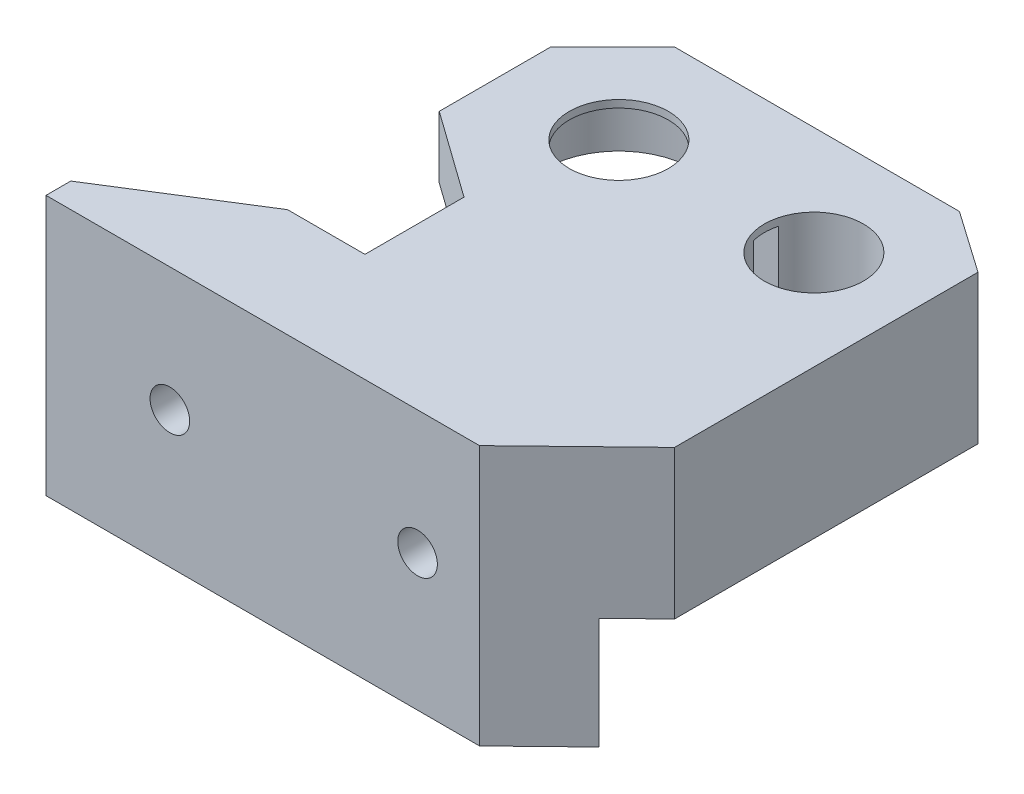
SolidWorks part; units mm, degrees
ref_plane "Front Plane" through (0, 0, 0) normal (0, 0, 1) x (1, 0, 0)
ref_plane "Top Plane" through (0, 0, 0) normal (0, 1, 0) x (1, 0, 0)
ref_plane "Right Plane" through (0, 0, 0) normal (1, 0, 0) x (0, 0, -1)
sketch "Sketch1" plane through (0, 0, 0) normal (0, 1, 0) x (1, 0, 0)
  line L0 (0, 0) -> (15.75, 0) construction
  line L5 (-4.25, 8.75) -> (18.75, 8.75)
  line L6 (18.75, 8.75) -> (23.75, 5.25)
  line L7 (23.75, 5.25) -> (23.75, -19.25)
  line L8 (23.75, -19.25) -> (15.75, -27)
  line L9 (15.75, -27) -> (-19.25, -27)
  line L10 (-19.25, -27) -> (-19.25, -25)
  line L11 (-19.25, -25) -> (-8.5, -18.25)
  line L12 (-8.5, -18.25) -> (-2.25, -18.25)
  line L13 (-2.25, -18.25) -> (-2.25, -10.25)
  line L14 (-2.25, -10.25) -> (-9.25, -5.25)
  line L15 (-9.25, -5.25) -> (-9.25, 3.75)
  line L16 (-9.25, 3.75) -> (-4.25, 8.75)
  line L17 (15.75, 0) -> (23.75, 0) construction
  circle A0 centre (0, 0) radius 4
  circle A1 centre (15.75, 0) radius 4
  point P0 (0, 0)
  dimension "D2" = 8
  dimension "D3" = 8
  dimension "D1" = 15.75
  dimension "D4" = 23
  dimension "D5" = 5
  dimension "D6" = 3.5
  dimension "D7" = 24.5
  dimension "D8" = 8
  dimension "D9" = 8.75
  dimension "D10" = 5
  dimension "D11" = 5
  dimension "D12" = 7
  dimension "D13" = 5
  dimension "D14" = 9
  dimension "D15" = 8
  dimension "D16" = 7.75
  dimension "D17" = 35
  dimension "D18" = 6.25
  dimension "D19" = 6.75
  dimension "D20" = 2
extrude "Boss-Extrude1" add sketch "Sketch1" along normal blind 5
sketch "Sketch2" plane through (0, 0, 0) normal (0, -1, 0) x (1, 0, 0)
  line L0 (23.75, 19.25) -> (23.75, -5.25)
  line L1 (23.75, -5.25) -> (20.25, -5.25)
  line L2 (20.25, -5.25) -> (20.25, 18.25)
  line L3 (20.25, 18.25) -> (-8.5, 18.25)
  line L4 (-8.5, 18.25) -> (-14.8704, 22.25)
  line L5 (-8.5, 18.25) -> (-19.25, 25) construction
  line L6 (-14.8704, 22.25) -> (20.6532, 22.25)
  line L7 (15.75, 27) -> (23.75, 19.25) construction
  line L8 (20.6532, 22.25) -> (23.75, 19.25)
  dimension "D1" = 3.5
  dimension "D2" = 4
extrude "Boss-Extrude2" add sketch "Sketch2" along normal blind 7
sketch "Sketch3" plane through (0, 0, 0) normal (0, -1, 0) x (1, 0, 0)
  line L5 (-14.8704, 22.25) -> (20.6532, 22.25)
  line L6 (20.6532, 22.25) -> (15.75, 27)
  line L7 (15.75, 27) -> (-19.25, 27)
  line L8 (-19.25, 27) -> (-19.25, 25)
  line L9 (-19.25, 25) -> (-14.8704, 22.25)
  line L10 (-14.8704, 22.25) -> (20.6532, 22.25)
  line L11 (20.6532, 22.25) -> (15.75, 27)
  line L12 (15.75, 27) -> (-19.25, 27)
  line L13 (-19.25, 27) -> (-19.25, 25)
  line L14 (-19.25, 25) -> (-14.8704, 22.25)
  dimension "D1" = 0
extrude "Boss-Extrude3" add sketch "Sketch3" along normal blind 16
sketch "Sketch6" plane through (0, 0, 0) normal (0, -1, 0) x (1, 0, 0)
  circle A0 centre (15.75, 0) radius 7
  circle A1 centre (15.75, 0) radius 4
  dimension "D1" = 14
extrude "Boss-Extrude4" add sketch "Sketch6" along normal blind 2.5
sketch "Sketch4" plane through (0, 0, 0) normal (0, -1, 0) x (1, 0, 0)
  line L0 (0, 0) -> (12.25, 0) construction
  line L1 (5.8838, -1) -> (12.3959, -1)
  line L2 (5.8838, 1) -> (12.3959, 1)
  line L3 (0, -1) -> (15.75, -1) construction
  line L4 (0, 1) -> (15.75, 1) construction
  line L5 (0, 0) -> (15.75, 0) construction
  arc A0 (5.8838, 1) -> (5.8838, -1) centre (0, 0) ccw
  arc A2 (12.3959, 1) -> (12.3959, -1) centre (15.75, 0) ccw
  dimension "D1" = 1
  dimension "D2" = 1
extrude "Cut-Extrude1" cut sketch "Sketch4" against normal blind 4.4
sketch "Sketch7" plane through (0, 4.4, 0) normal (0, -1, 0) x (1, 0, 0)
  line L2 (5.8838, -1) -> (11.877, -1)
  line L3 (11.877, 1) -> (5.8838, 1)
  line L4 (5.8838, -1) -> (11.877, -1)
  line L5 (11.877, 1) -> (5.8838, 1)
  arc A2 (5.8838, 1) -> (5.8838, -1) centre (0, 0) ccw
  arc A3 (11.877, 1) -> (11.877, -1) centre (15.75, 0) ccw
  arc A4 (5.8838, 1) -> (5.8838, -1) centre (0, 0) ccw
  arc A5 (11.877, 1) -> (11.877, -1) centre (15.75, 0) ccw
  dimension "D1" = 0
extrude "Cut-Extrude2" cut sketch "Sketch7" along normal through all
sketch "Sketch8" plane through (0, 0, 27) normal (0, 0, 1) x (1, 0, 0)
  line L0 (10.75, -5) -> (-9.25, -5) construction
  line L1 (-19.25, 5) -> (15.75, 5) construction
  line L2 (-19.25, 5) -> (-19.25, -16) construction
  circle A0 centre (10.75, -5) radius 1.6
  circle A1 centre (-9.25, -5) radius 1.6
  dimension "D1" = 3.2
  dimension "D2" = 3.2
  dimension "D3" = 20
  dimension "D4" = 10
  dimension "D5" = 10
extrude "Cut-Extrude3" cut sketch "Sketch8" against normal through all
sketch "Sketch9" plane through (0, 0, 18.25) normal (0, 0, -1) x (-1, 0, 0)
  circle A0 centre (-10.75, -5) radius 3
  circle A1 centre (9.25, -5) radius 3
  dimension "D1" = 6
  dimension "D2" = 6
extrude "Cut-Extrude4" cut sketch "Sketch9" against normal blind 4
